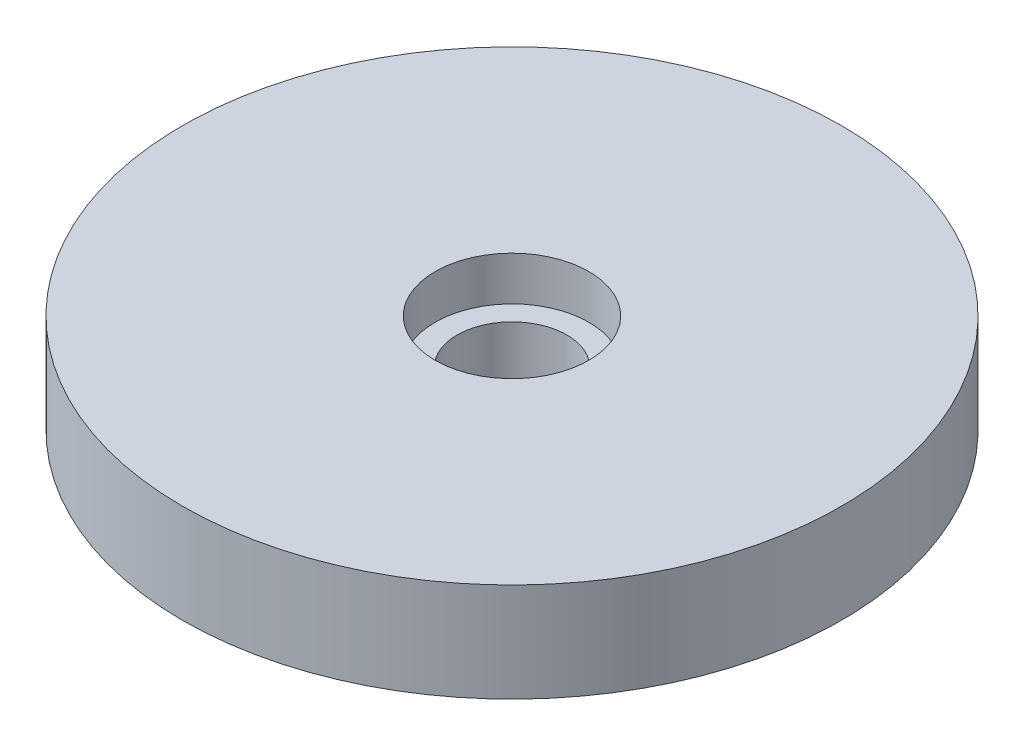
SolidWorks part; units mm, degrees
ref_plane "Front Plane" through (0, 0, 0) normal (0, 0, 1) x (1, 0, 0)
ref_plane "Top Plane" through (0, 0, 0) normal (0, 1, 0) x (1, 0, 0)
ref_plane "Right Plane" through (0, 0, 0) normal (1, 0, 0) x (0, 0, -1)
sketch "Sketch1" plane through (0, 0, 0) normal (0, 1, 0) x (1, 0, 0)
  circle A0 centre (0, 0) radius 38.1
  circle A1 centre (0, 0) radius 25.4
  dimension "D1" = 76.2
  dimension "D2" = 50.8
extrude "Boss-Extrude3" add sketch "Sketch1" along normal blind 6.35
extrude "Boss-Extrude4" add sketch "Sketch1<3>" along normal blind 6.35 contours A1 region at (0, 0, 0)
sketch "Sketch1<3>" plane through (0, 0, 0) normal (0, 1, 0) x (1, 0, 0) same geometry as "Sketch1"
sketch "Sketch2" plane through (0, 0, 0) normal (0, -1, 0) x (1, 0, 0)
  circle A0 centre (0, 31.2664) radius 3.81
  circle A1 centre (0, 0) radius 38.1 construction
  circle A2 centre (26.9549, 15.704) radius 3.81
  circle A3 centre (26.9549, -15.4208) radius 3.81
  circle A4 centre (0, -30.9832) radius 3.81
  circle A5 centre (-26.9549, -15.4208) radius 3.81
  circle A6 centre (-26.9549, 15.704) radius 3.81
  point P18 (0, 0.1416)
  dimension "D1" = 7.62
  dimension "D2" = 31.2664
  dimension "D4" = 53.9097
  dimension "D3" = 6
extrude "Cut-Extrude1" cut sketch "Sketch2" against normal blind 2.54 contours A0 | A2 | A3 | A4 | A5 | A6
sketch "Sketch3" plane through (0, 6.35, 0) normal (0, 1, 0) x (1, 0, 0)
  circle A0 centre (0, 0) radius 6.35
  dimension "D1" = 12.7
extrude "Cut-Extrude2" cut sketch "Sketch3" against normal through all contours A0
sketch "Sketch4" plane through (0, 6.35, 0) normal (0, 1, 0) x (1, 0, 0)
  circle A0 centre (0, 0) radius 38.1
  circle A1 centre (0, 0) radius 8.89
  dimension "D1" = 76.2
  dimension "D2" = 17.78
extrude "Boss-Extrude5" add sketch "Sketch4" along normal blind 5.08
